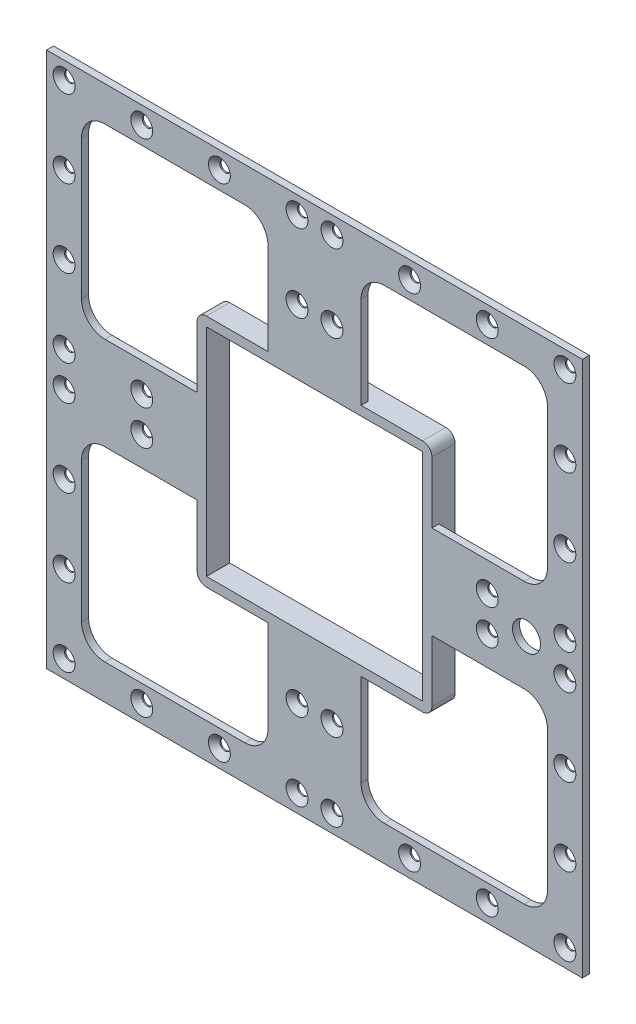
SolidWorks part; units mm, degrees
material "6061-T6 (SS)"
ref_plane "Alzado" through (0, 0, 0) normal (0, 0, 1) x (1, 0, 0)
ref_plane "Planta" through (0, 0, 0) normal (0, 1, 0) x (1, 0, 0)
ref_plane "Vista lateral" through (0, 0, 0) normal (1, 0, 0) x (0, 0, -1)
sketch "Sketch1" plane through (0, 0, 0) normal (0, 0, 1) x (1, 0, 0)
  line L1 (-115, 115) -> (115, 115)
  line L2 (-115, 115) -> (-115, -115)
  line L3 (-115, -115) -> (115, -115)
  line L4 (115, 115) -> (115, -115)
  line L5 (-115, 115) -> (115, -115) construction
  line L6 (-115, -115) -> (115, 115) construction
  point P0 (0, 0)
  dimension "D1" = 230
extrude "Boss-Extrude1" add sketch "Sketch1" along normal blind 3
sketch "Sketch2" plane through (0, 0, 0) normal (0, 0, 1) x (1, 0, 0)
  line L0 (-115, 115) -> (-115, -115) construction
  line L1 (-100, 100) -> (-20, 100)
  line L2 (-100, 100) -> (-100, 20)
  line L3 (-100, 20) -> (-20, 20)
  line L4 (-20, 100) -> (-20, 20)
  line L5 (-100, 100) -> (-20, 20) construction
  line L6 (-100, 20) -> (-20, 100) construction
  line L7 (115, 115) -> (-115, 115) construction
  point P0 (-60, 60)
  point P9 (-60, 100)
  dimension "D1" = 80
  dimension "D2" = 80
  dimension "D3" = 15
  dimension "D4" = 15
extrude "Cut-Extrude2" cut sketch "Sketch2" along normal through all
fillet "Fillet1" radius 10 4 edges at (-100, 100, 1.5) (-20, 100, 1.5) (-20, 20, 1.5) (-100, 20, 1.5)
pattern_linear "LPattern2" count 2 spacing 120 along (0, -1, 0) count 2 spacing 120 along (1, 0, 0) of "Fillet1", "Cut-Extrude2"
sketch "Sketch11" plane through (0, 0, 3) normal (0, 0, 1) x (1, 0, 0)
  line L0 (-115, 115) -> (-115, -115) construction
  line L1 (115, 115) -> (-115, 115) construction
  point P0 (-107.5, 107.5)
  dimension "D1" = 7.5
  dimension "D2" = 7.5
hole_wizard "CSK for M4 Flat Head Machine Screw4" positions "Sketch11" profile "Sketch12" countersink size "M4" standard "ANSI Metric" end condition through all
sketch "Sketch12" plane through (-107.5, 107.5, 3) normal (1, 0, 0) x (0, -1, 0)
  line L0 (0, 0) -> (0, 3)
  line L1 (0, 3) -> (2.25, 3)
  line L2 (2.25, 3) -> (2.25, 2.45)
  line L3 (2.25, 2.45) -> (4.7, 0)
  line L5 (4.7, 0) -> (0, 0)
  line L6 (-2.25, 2.45) -> (-4.7, 0) construction
  line L11 (0, -6.35) -> (0, 107.95) construction
  dimension "Thru Hole Dia." = 4.5
  dimension "Thru Hole Depth" = 3
  dimension "Near C'Sink Dia." = 9.4
  dimension "Near C'Sink Angle" = 90
sketch "Sketch13" plane through (0, 0, 3) normal (0, 0, 1) x (1, 0, 0)
  line L0 (0, 115) -> (0, -115) construction
  line L1 (115, 115) -> (-115, 115) construction
  line L2 (-115, -115) -> (115, -115) construction
  line L3 (-115, 0) -> (115, 0) construction
  line L4 (-115, 115) -> (-115, -115) construction
  line L5 (115, -115) -> (115, 115) construction
pattern_linear "LPattern8" count 4 spacing 33.3333 along (1, 0, 0) count 4 spacing 33.3333 along (0, -1, 0) skipping (1, 1), (1, 2), (2, 1), (2, 2) of "CSK for M4 Flat Head Machine Screw4"
mirror "Mirror1" about plane through (0, 0, 0) normal (1, 0, 0) of "LPattern8" second plane through (0, 0, 0) second plane normal (0, 1, 0)
sketch "Sketch14" plane through (0, 0, 3) normal (0, 0, 1) x (1, 0, 0)
  line L1 (-49, 49) -> (49, 49)
  line L2 (-49, 49) -> (-49, -49)
  line L3 (-49, -49) -> (49, -49)
  line L4 (49, 49) -> (49, -49)
  line L5 (-49, 49) -> (49, -49) construction
  line L6 (-49, -49) -> (49, 49) construction
  point P0 (0, 0)
  dimension "D1" = 98
  dimension "D2" = 98
extrude "Cut-Extrude3" cut sketch "Sketch14" against normal up to next
sketch "Sketch15" plane through (0, 0, 3) normal (0, 0, 1) x (1, 0, 0)
  line L1 (-50.4, 50.4) -> (50.4, 50.4)
  line L2 (-50.4, 50.4) -> (-50.4, -50.4)
  line L3 (-50.4, -50.4) -> (50.4, -50.4)
  line L4 (50.4, 50.4) -> (50.4, -50.4)
  line L5 (-50.4, 50.4) -> (50.4, -50.4) construction
  line L6 (-50.4, -50.4) -> (50.4, 50.4) construction
  line L7 (-46.4, 46.4) -> (46.4, 46.4)
  line L8 (-46.4, 46.4) -> (-46.4, -46.4)
  line L9 (-46.4, -46.4) -> (46.4, -46.4)
  line L10 (46.4, 46.4) -> (46.4, -46.4)
  line L11 (-46.4, 46.4) -> (46.4, -46.4) construction
  line L12 (-46.4, -46.4) -> (46.4, 46.4) construction
  point P0 (0, 0)
  point P6 (0, 0)
  dimension "D1" = 92.8
  dimension "D2" = 4
extrude "Boss-Extrude2" add sketch "Sketch15" against normal blind 10
fillet "Fillet2" radius 4 4 edges at (-50.4, -50.4, -2) (50.4, -50.4, -2) (50.4, 50.4, -2) (-50.4, 50.4, -2)
sketch "Sketch16" plane through (0, 0, 3) normal (0, 0, 1) x (1, 0, 0)
  circle A0 centre (91, 0) radius 6
  dimension "D1" = 12
extrude "Cut-Extrude4" cut sketch "Sketch16" against normal up to next
